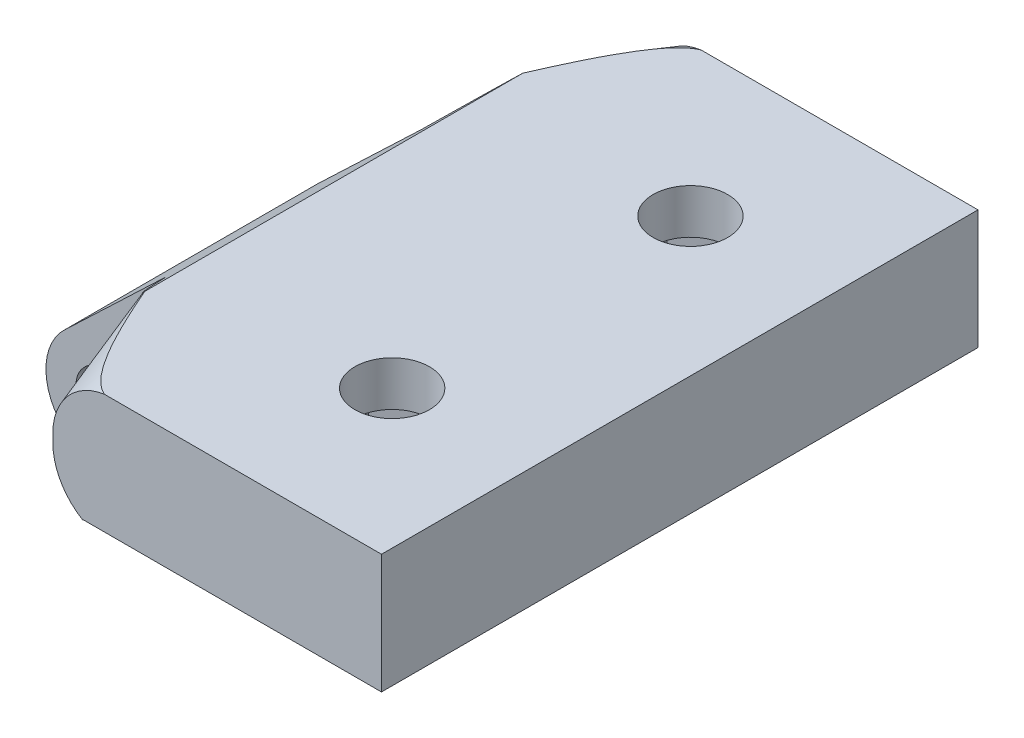
SolidWorks part; units mm, degrees
ref_plane "Top Plane" through (0, 0, 0) normal (0, 0, 1) x (1, 0, 0)
ref_plane "Right Plane" through (0, 0, 0) normal (0, 1, 0) x (1, 0, 0)
ref_plane "Front Plane" through (0, 0, 0) normal (1, 0, 0) x (0, 0, -1)
sketch "Sketch1" plane through (0, 0, 0) normal (0, 0, 1) x (1, 0, 0)
  line L0 (-2.7586, 2.8966) -> (6.8, 12)
  line L1 (6.8, 12) -> (30, 12)
  line L2 (30, 12) -> (30, 4)
  line L3 (30, 4) -> (10, 4)
  line L4 (10, 4) -> (2.7586, -2.8966)
  line L5 (10, 4) -> (4.4828, 9.7931) construction
  arc A1 (-2.7586, 2.8966) -> (2.7586, -2.8966) centre (0, 0) ccw
  circle A3 centre (0, 0) radius 2
  arc A4 (2.7586, -2.8966) -> (-2.7586, 2.8966) centre (0, 0) ccw construction
  point P1 (0, 0)
  dimension "D3" = 4
  dimension "D4" = 4
  dimension "D1" = 10
  dimension "D2" = 20
extrude "Boss-Extrude1" add sketch "Sketch1" against normal mid plane 40
sketch "Sketch2" plane through (0, 4, 0) normal (0, -1, 0) x (1, 0, 0)
  line L0 (10, -20) -> (10, 20) construction
  line L1 (8, 8.5) -> (-12, 8.5)
  line L2 (8, 0) -> (8, -8.5) construction
  line L3 (8, -8.5) -> (-12, -8.5)
  line L4 (-12, 8.5) -> (-12, -8.5) construction
  line L5 (8, 0) -> (10, 0) construction
  line L6 (-12, 8.5) -> (-12, 25)
  line L7 (8, -25) -> (-12, -25)
  line L8 (8, -25) -> (8, -8.5)
  line L9 (8, 25) -> (-12, 25)
  line L10 (-12, -25) -> (-12, -8.5)
  line L11 (-12, -8.5) -> (-12, 8.5) construction
  line L12 (8, 8.5) -> (8, 0) construction
  line L13 (8, 8.5) -> (8, 25)
  line L14 (8, 0) -> (8, 8.5) construction
  line L15 (8, -8.5) -> (8, 0) construction
  dimension "D1" = 20
  dimension "D2" = 17
  dimension "D3" = 2
  dimension "D4" = 50
extrude "Cut-Extrude1" cut sketch "Sketch2" against normal through all both and the other way through all
fillet "Fillet1" radius 4 4 edges at (8, 2.0952, -14.25) (8, 12, -14.25) (8, 12, 14.25) (8, 2.0952, 14.25)
chamfer "Chamfer1" distance 4 angle 71 6 edges at (9.1716, 10.8284, -8.5) (8, 7.7321, -8.5) (8.5359, 5.4641, -8.5) (9.1716, 10.8284, 8.5) (8, 7.7321, 8.5) (8.5359, 5.4641, 8.5)
sketch "Sketch4" plane through (0, 12, 0) normal (0, 1, 0) x (1, 0, 0)
  line L0 (20.7156, -20) -> (20.7156, 0) construction
  line L2 (30, -20) -> (11.4312, -20) construction
  line L3 (20.7156, 0) -> (30, 0) construction
  line L4 (30, 20) -> (30, -20) construction
  circle A0 centre (20.7156, -10) radius 2.5
  point P6 (0, 0)
  point P10 (0, 0)
  point P11 (0, 0)
  dimension "D1" = 5
extrude "Cut-Extrude2" cut sketch "Sketch4" against normal through all
sketch "Sketch5" plane through (0, 12, 0) normal (0, 1, 0) x (1, 0, 0)
  line L0 (20.7156, -14.3301) -> (24.4656, -12.1651)
  line L1 (24.4656, -12.1651) -> (24.4656, -7.8349)
  line L2 (24.4656, -7.8349) -> (20.7156, -5.6699)
  line L3 (20.7156, -5.6699) -> (16.9656, -7.8349)
  line L4 (16.9656, -7.8349) -> (16.9656, -12.1651)
  line L5 (16.9656, -12.1651) -> (20.7156, -14.3301)
  circle A0 centre (20.7156, -10) radius 4.3301 construction
  dimension "D1" = 7.5
extrude "Cut-Extrude3" cut sketch "Sketch5" against normal through all from offset 3 offset against normal yes
mirror "Mirror1" about plane through (0, 0, 0) normal (0, 0, 1) of "Cut-Extrude3", "Cut-Extrude2"
